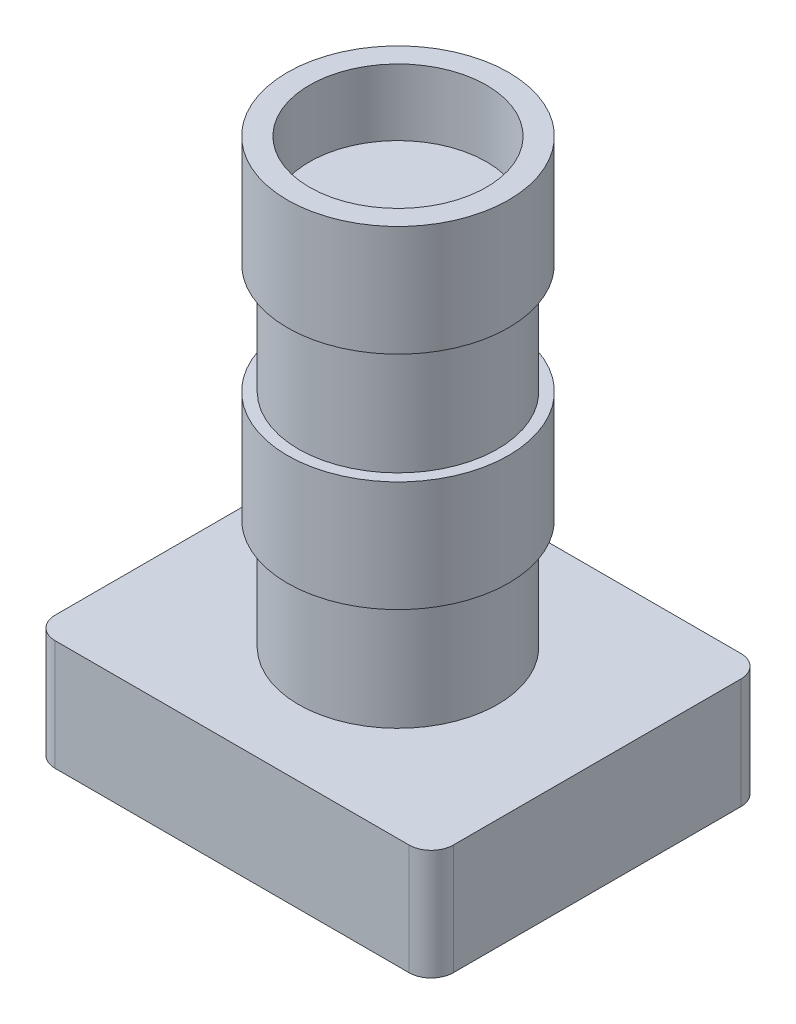
SolidWorks part; units mm, degrees
ref_plane "Front Plane" through (0, 0, 0) normal (0, 0, 1) x (1, 0, 0)
ref_plane "Top Plane" through (0, 0, 0) normal (0, 1, 0) x (1, 0, 0)
ref_plane "Right Plane" through (0, 0, 0) normal (1, 0, 0) x (0, 0, -1)
sketch "Sketch1" plane through (0, 0, 0) normal (0, 1, 0) x (1, 0, 0)
  line L0 (-8.4143, 0) -> (6, 0) construction
  line L1 (0, -5.6176) -> (0, 6.2927) construction
  line L2 (6, -5) -> (6, 5) construction
  line L3 (4.5, -5) -> (4.5, 5)
  line L4 (7.5, -5) -> (7.5, 5)
  line L5 (-6, -5) -> (-6, 5) construction
  line L6 (-4.5, -5) -> (-4.5, 5)
  line L7 (-7.5, -5) -> (-7.5, 5)
  line L9 (-8, 7.5) -> (8, 7.5)
  line L10 (-9, 6.5) -> (-9, -6.5)
  line L11 (-8, -7.5) -> (8, -7.5)
  line L12 (9, 6.5) -> (9, -6.5)
  line L13 (-9, 7.5) -> (9, -7.5) construction
  line L14 (-9, -7.5) -> (9, 7.5) construction
  circle A0 centre (0, 0) radius 4
  arc A1 (4.5, -5) -> (7.5, -5) centre (6, -5) ccw
  arc A2 (7.5, 5) -> (4.5, 5) centre (6, 5) ccw
  arc A3 (-4.5, -5) -> (-7.5, -5) centre (-6, -5) cw
  arc A4 (-7.5, 5) -> (-4.5, 5) centre (-6, 5) cw
  arc A5 (-9, -6.5) -> (-8, -7.5) centre (-8, -6.5) ccw
  arc A6 (-8, 7.5) -> (-9, 6.5) centre (-8, 6.5) ccw
  arc A7 (8, 7.5) -> (9, 6.5) centre (8, 6.5) cw
  arc A8 (8, -7.5) -> (9, -6.5) centre (8, -6.5) ccw
  circle A9 centre (0, 0) radius 4.5
  point P9 (6, 0)
  point P16 (-6, 0)
  dimension "D1" = 8
  dimension "D5" = 1
  dimension "D2" = 3
  dimension "D3" = 10
  dimension "D4" = 12
  dimension "D6" = 18
  dimension "D7" = 15
  dimension "D8" = 0.5
extrude "Boss-Extrude1" add sketch "Sketch1" along normal blind 5 contours L11 A8 L12 A7 L9 A6 L10 A5 A9 L3 A2 L4 A1 L6 A3 L7 A4 | A4 L7 A3 L6 | A9 A0 | A0 | L4 A2 L3 A1 region at (-6, 0, 0) region at (0, 0, 4.3727) region at (6, 0, 0) region at (0, 0, -7.2657) region at (0, 0, 0)
extrude "Cut-Extrude2" cut sketch "Sketch1<5>" along normal through all contours A0 region at (0, 0, 0)
sketch "Sketch1<5>" plane through (0, 0, 0) normal (0, 1, 0) x (1, 0, 0) same geometry as "Sketch1"
extrude "Boss-Extrude4" add sketch "Sketch1<6>" along normal blind 10 contours A9 A0 region at (0, 0, 4.3727)
sketch "Sketch1<6>" plane through (0, 0, 0) normal (0, 1, 0) x (1, 0, 0) same geometry as "Sketch1"
sketch "Sketch3" plane through (0, 10, 0) normal (0, 1, 0) x (1, 0, 0)
  circle A0 centre (0, 0) radius 5
  dimension "D1" = 10
extrude "Boss-Extrude5" add sketch "Sketch3" along normal blind 5
sketch "Sketch4" plane through (0, 15, 0) normal (0, 1, 0) x (1, 0, 0)
  circle A0 centre (0, 0) radius 4.5 construction
  circle A1 centre (0, 0) radius 4.5
extrude "Boss-Extrude6" add sketch "Sketch4" along normal blind 5
sketch "Sketch5" plane through (0, 20, 0) normal (0, 1, 0) x (1, 0, 0)
  circle A0 centre (0, 0) radius 5 construction
  circle A1 centre (0, 0) radius 5
extrude "Boss-Extrude7" add sketch "Sketch5" along normal blind 5
sketch "Sketch7" plane through (0, 10, 0) normal (0, -1, 0) x (1, 0, 0)
  circle A0 centre (0, 0) radius 5 construction
  circle A1 centre (0, 0) radius 5
  circle A2 centre (0, 0) radius 4.5 construction
  circle A3 centre (0, 0) radius 4.5
sketch "Sketch8" plane through (0, 25, 0) normal (0, 1, 0) x (1, 0, 0)
  circle A0 centre (0, 0) radius 4
  dimension "magnet OD" = 8
extrude "Cut-Extrude3" cut sketch "Sketch8" against normal blind 3
